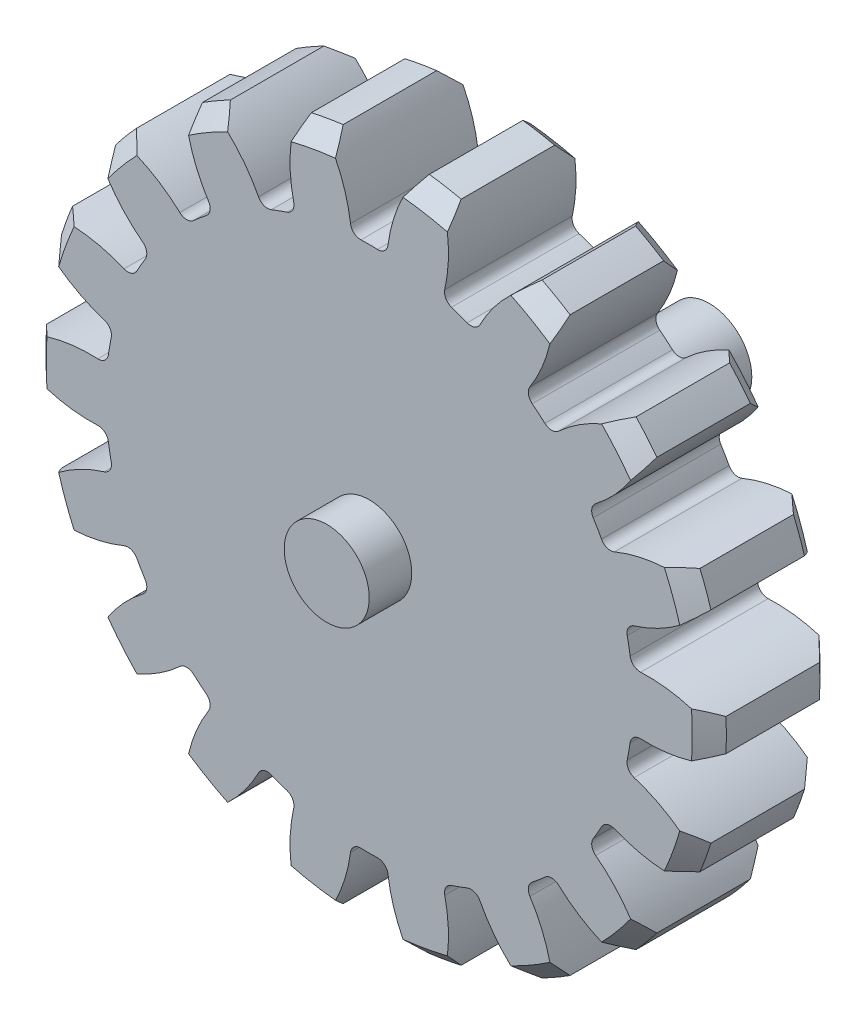
SolidWorks part; units mm, degrees
ref_plane "Přední rovina" through (0, 0, 0) normal (0, 0, 1) x (1, 0, 0)
ref_plane "Horní rovina" through (0, 0, 0) normal (0, 1, 0) x (1, 0, 0)
ref_plane "Pravá rovina" through (0, 0, 0) normal (1, 0, 0) x (0, 0, -1)
sketch "Skica1" plane through (0, 0, 0) normal (0, 0, 1) x (1, 0, 0)
  circle A0 centre (0, 0) radius 20
  circle A1 centre (0, 0) radius 18 construction
  dimension "D1" = 40
  dimension "D2" = 36
extrude "Přidat vysunutím1" add sketch "Skica1" along normal blind 7.5
sketch "Skica2" plane through (0, 0, 0) normal (0, 0, 1) x (1, 0, 0)
  line L0 (0, 20) -> (0, 0) construction
  line L1 (0, 0) -> (6.8404, 18.7939) construction
  line L2 (0, 0) -> (3.473, 19.6962) construction
  line L3 (0, 0) -> (-1.0473, 15.4646) construction
  line L4 (-1.5688, 17.9315) -> (1.5688, 17.9315) construction
  line L5 (1.5688, 17.9315) -> (4.6587, 17.3867) construction
  line L6 (-2.2744, 19.8703) -> (0, 13.6213) construction
  arc A0 (1.0473, 15.4646) -> (-1.0473, 15.4646) centre (0, 0) ccw
  circle A1 centre (0, 0) radius 16 construction
  circle A2 centre (0, 0) radius 20 construction
  arc A3 (-2.5335, 19.8389) -> (-1.0473, 15.4646) centre (-10.0152, 14.8573) cw
  arc A4 (2.5335, 19.8389) -> (1.0473, 15.4646) centre (10.0152, 14.8573) ccw
  circle A5 centre (0, 0) radius 18 construction
  arc A6 (-2.5335, 19.8389) -> (2.5335, 19.8389) centre (0, 0) cw
  dimension "D2" = 4.5
  dimension "D3" = 0.5
  dimension "D4" = 20
  dimension "D5" = 20
  dimension "D6" = 0.5
extrude "Odebrat vysunutím1" cut sketch "Skica2" along normal blind 7.5
fillet "Zaoblit2" radius 0.6 2 edges at (1.0473, 15.4646, 3.75) (-1.0473, 15.4646, 3.75)
chamfer "Zkosení1" distance 1 2 edges at (0, -20, 0) (0, -20, 7.5)
pattern_circular "Kruhové pole1" count 18 every 20 about axis through (0, 0, 7.5) along (0, 0, -1) of "Odebrat vysunutím1", "Zaoblit2"
sketch "Skica3" plane through (0, 0, 0) normal (0, 0, 1) x (1, 0, 0)
  circle A0 centre (0, 0) radius 2.5
  dimension "D1" = 5
extrude "Přidat vysunutím2" add sketch "Skica3" against normal blind 12.5 and the other way blind 10
equation "\"Module\"= 2mm"
equation "\"Number of teeth\" = 18"
equation "\"Pressure angle\"= 20"
equation "\"D1@Skica1\"=(\"Number of teeth\" + 2) * \"Module\""
equation "\"D2@Skica1\"= \"Number of teeth\" * \"Module\""
equation "\"D1@Skica2\"= \"Module\" * 2"
equation "\"D2@Skica2\"=\"Module\" * if( \"Module\" => 1.25, 2.25, 2.4 )"
equation "\"D4@Skica2\"= 360 / \"Number of teeth\""
equation "\"D5@Skica2\"=\"Pressure angle\""
equation "\"DC1@Zaoblit\"= 0.3 * \"Module\""
equation "\"D1@Kruhové pole1\"=\"Number of teeth\""
equation "\"D2@Kruhové pole1\"= 360 / \"Number of teeth\""
